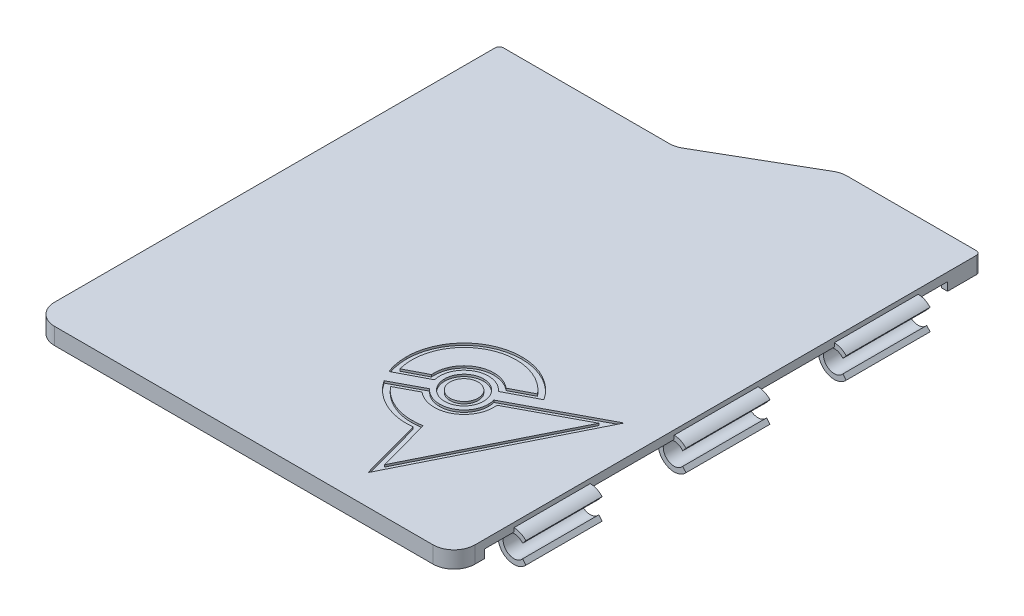
SolidWorks part; units mm, degrees
ref_plane "Front Plane" through (0, 0, 0) normal (0, 0, 1) x (1, 0, 0)
ref_plane "Top Plane" through (0, 0, 0) normal (0, 1, 0) x (1, 0, 0)
ref_plane "Right Plane" through (0, 0, 0) normal (1, 0, 0) x (0, 0, -1)
sketch "Sketch1" plane through (0, 0, 0) normal (0, 1, 0) x (1, 0, 0)
  line L0 (63.6333, 61.8247) -> (63.6333, 80.2409) construction
  line L1 (63.6333, -79.34) -> (-63.6333, -79.34)
  line L2 (63.6333, -79.34) -> (63.6333, 80.0409)
  line L4 (-63.6333, -79.34) -> (-63.6333, 61.6247)
  line L5 (-57.2833, -79.34) -> (57.2833, -79.34) construction
  line L6 (23.1126, 80.2409) -> (62.3633, 80.2409) construction
  line L7 (-63.6333, 92.3071) -> (-63.6333, 63.0947) construction
  line L11 (-63.6333, 61.6247) -> (-10.4331, 61.6247)
  line L12 (21.4647, 80.0409) -> (63.6333, 80.0409)
  line L13 (-10.4331, 61.6247) -> (21.4647, 80.0409)
  line L14 (-9.0132, 62.6755) -> (19.9376, 79.3902) construction
  line L15 (-62.3633, 61.8247) -> (-12.1882, 61.8247) construction
  point P0 (0, 0)
  dimension "D1" = 0.2
  dimension "D2" = 0.2
  dimension "D3" = 0.2
extrude "Boss-Extrude1" add sketch "Sketch1" along normal up to surface (5.0667 mm away)
ref_plane "Plane1" through (0, 0, -61.1897) normal (0, 0, 1) x (1, 0, 0)
sketch "Sketch2" plane through (0, 0, -61.1897) normal (0, 0, 1) x (1, 0, 0)
  circle A0 centre (63.6333, -1.1598) radius 4.826
  circle A1 centre (63.6333, -1.1598) radius 3.302
  point P3 (0, 0)
  point P5 (63.6333, -1.1598)
  dimension "D1" = 9.652
  dimension "D2" = 6.604
extrude "Boss-Extrude2" add sketch "Sketch2" along normal offset from surface (122.3795 mm away) 0.635
sketch "Sketch3" plane through (0, 0, 61.1897) normal (0, 0, 1) x (1, 0, 0)
  arc A0 (60.5417, 0) -> (63.6333, 2.1422) centre (63.6333, -1.1598) ccw construction
  circle A1 centre (63.6333, -1.1598) radius 3.302
extrude "Cut-Extrude1" cut sketch "Sketch3" against normal up to surface (122.3795 mm away) up to face at (63.8751, -1.4825, -61.1897)
sketch "Sketch4" plane through (0, 0, 0) normal (0, -1, 0) x (1, 0, 0)
  line L12 (60.5417, 63.0947) -> (61.7283, 63.0947)
  line L13 (60.5417, 63.0947) -> (61.7283, 63.0947)
  line L14 (61.7283, -63.0947) -> (60.5417, -63.0947)
  line L15 (61.7283, -63.0947) -> (60.5417, -63.0947)
  line L24 (61.7283, 63.0947) -> (61.7283, 77.435)
  line L25 (61.7283, 77.435) -> (-61.7283, 77.435)
  line L26 (-61.7283, 77.435) -> (-61.7283, -59.7197)
  line L27 (-61.7283, -59.7197) -> (-9.9227, -59.7197)
  line L28 (-9.9227, -59.7197) -> (21.9751, -78.1359)
  line L29 (21.9751, -78.1359) -> (61.7283, -78.1359)
  line L30 (61.7283, -78.1359) -> (61.7283, -63.0947)
  line L31 (60.5417, -63.0947) -> (57.0438, -63.0947)
  line L32 (57.0438, -63.0947) -> (57.0438, 63.0947)
  line L33 (57.0438, 63.0947) -> (60.5417, 63.0947)
  line L34 (61.7283, 63.0947) -> (61.7283, 77.435)
  line L35 (61.7283, 77.435) -> (-61.7283, 77.435)
  line L36 (-61.7283, 77.435) -> (-61.7283, -59.7197)
  line L37 (-61.7283, -59.7197) -> (-9.9227, -59.7197)
  line L38 (-9.9227, -59.7197) -> (21.9751, -78.1359)
  line L39 (21.9751, -78.1359) -> (61.7283, -78.1359)
  line L40 (61.7283, -78.1359) -> (61.7283, -63.0947)
  line L41 (60.5417, -63.0947) -> (57.0438, -63.0947)
  line L42 (57.0438, -63.0947) -> (57.0438, 63.0947)
  line L43 (57.0438, 63.0947) -> (60.5417, 63.0947)
  dimension "D1" = 1.905
extrude "Cut-Extrude2" cut sketch "Sketch4" against normal offset from surface (3.1617 mm away) 1.905 up to face at (1.8386, 5.0667, -20.7752)
sketch "Sketch6" plane through (63.6333, 0, 0) normal (1, 0, 0) x (0, 0, -1)
  line L0 (0, 12.3819) -> (0, -18.9186) construction
  line L1 (-61.1897, 0) -> (-70.0797, 0)
  line L2 (-61.1897, 0) -> (-61.1897, 2.54)
  line L3 (-61.1897, 2.54) -> (-70.0797, 2.54)
  line L4 (-70.0797, 0) -> (-70.0797, 2.54)
  line L5 (70.0797, 0) -> (70.0797, 2.54)
  line L6 (61.1897, 2.54) -> (70.0797, 2.54)
  line L7 (61.1897, 0) -> (61.1897, 2.54)
  line L8 (61.1897, 0) -> (70.0797, 0)
  line L9 (-69.4447, 1.905) -> (-69.4447, 0) construction
  line L10 (-69.4447, 1.905) -> (-61.8247, 1.905) construction
  point P14 (-69.4447, 0.9525)
  dimension "D1" = 0.635
  dimension "D2" = 0.635
extrude "Cut-Extrude3" cut sketch "Sketch6" against normal blind 6.35
sketch "Sketch7" plane through (0, 0, 0) normal (0, 0, 1) x (1, 0, 0)
  line L0 (63.6333, 4.337) -> (63.6333, 2.54)
  line L1 (63.6333, 5.0667) -> (63.6333, 0) construction
  line L2 (63.6333, 2.54) -> (61.7283, 2.54)
  line L3 (61.7283, 2.54) -> (61.7283, 3.1617)
  line L4 (61.7283, 3.1617) -> (56.3001, 3.1617)
  line L5 (-61.7283, 3.1617) -> (61.7283, 3.1617) construction
  line L6 (56.3001, 3.1617) -> (56.3001, -6.3518)
  line L7 (56.3001, -6.3518) -> (72.4996, -6.3518)
  line L8 (72.4996, -6.3518) -> (72.4996, 4.337)
  line L9 (72.4996, 4.337) -> (63.6333, 4.337)
ref_plane "Plane2" through (0, 0, 12.7) normal (0, 0, 1) x (1, 0, 0)
ref_plane "Plane3" through (0, 0, -12.7) normal (0, 0, 1) x (1, 0, 0)
sketch "Sketch8" plane through (0, 0, 12.7) normal (0, 0, 1) x (1, 0, 0)
  line L0 (63.6333, 4.337) -> (63.6333, 2.54) construction
  line L1 (72.4996, -6.3518) -> (72.4996, 4.337) construction
  line L2 (72.4996, 4.337) -> (63.6333, 4.337) construction
  line L3 (63.6333, 2.54) -> (61.7283, 2.54) construction
  line L4 (61.7283, 2.54) -> (61.7283, 3.1617) construction
  line L5 (61.7283, 3.1617) -> (56.3001, 3.1617) construction
  line L6 (56.3001, 3.1617) -> (56.3001, -6.3518) construction
  line L7 (56.3001, -6.3518) -> (72.4996, -6.3518) construction
  line L8 (56.3001, -6.3518) -> (72.4996, -6.3518)
  line L9 (56.3001, 3.1617) -> (56.3001, -6.3518)
  line L10 (61.7283, 3.1617) -> (56.3001, 3.1617)
  line L11 (61.7283, 2.54) -> (61.7283, 3.1617)
  line L12 (63.6333, 2.54) -> (61.7283, 2.54)
  line L13 (63.6333, 4.337) -> (63.6333, 2.54)
  line L14 (72.4996, 4.337) -> (63.6333, 4.337)
  line L15 (72.4996, -6.3518) -> (72.4996, 4.337)
sketch "Sketch9" plane through (0, 0, -12.7) normal (0, 0, 1) x (1, 0, 0)
  line L0 (72.4996, -6.3518) -> (72.4996, 4.337) construction
  line L1 (72.4996, 4.337) -> (63.6333, 4.337) construction
  line L2 (63.6333, 4.337) -> (63.6333, 2.54) construction
  line L3 (63.6333, 2.54) -> (61.7283, 2.54) construction
  line L4 (61.7283, 2.54) -> (61.7283, 3.1617) construction
  line L5 (61.7283, 3.1617) -> (56.3001, 3.1617) construction
  line L6 (56.3001, 3.1617) -> (56.3001, -6.3518) construction
  line L7 (56.3001, -6.3518) -> (72.4996, -6.3518) construction
  line L8 (72.4996, -6.3518) -> (72.4996, 4.337)
  line L9 (56.3001, -6.3518) -> (72.4996, -6.3518)
  line L10 (56.3001, 3.1617) -> (56.3001, -6.3518)
  line L11 (61.7283, 3.1617) -> (56.3001, 3.1617)
  line L12 (61.7283, 2.54) -> (61.7283, 3.1617)
  line L13 (63.6333, 2.54) -> (61.7283, 2.54)
  line L14 (63.6333, 4.337) -> (63.6333, 2.54)
  line L15 (72.4996, 4.337) -> (63.6333, 4.337)
extrude "Cut-Extrude4" cut sketch "Sketch9" against normal offset from surface (23.0897 mm away) 25.4
extrude "Cut-Extrude5" cut sketch "Sketch8" along normal blind 25.4
sketch "Sketch10" plane through (0, 0, 0) normal (0, -1, 0) x (1, 0, 0)
  line L0 (61.7283, 63.0947) -> (61.7283, 61.1897)
  line L1 (57.2833, 61.1897) -> (63.6333, 61.1897) construction
  line L2 (61.7283, 61.1897) -> (58.9488, 61.1897)
  line L3 (58.9488, 61.1897) -> (58.9488, -61.1897)
  line L4 (58.9488, -61.1897) -> (58.9488, -35.7897) construction
  line L5 (58.9488, -61.1897) -> (61.7283, -61.1897)
  line L6 (61.7283, -61.1897) -> (61.7283, -63.0947)
  line L7 (61.7283, -63.0947) -> (57.0438, -63.0947)
  line L8 (57.0438, -63.0947) -> (57.0438, 63.0947)
  line L9 (57.0438, 63.0947) -> (61.7283, 63.0947)
  line L10 (57.0438, 61.1897) -> (57.0438, 63.0947) construction
  line L11 (57.0438, 63.0947) -> (57.0438, 38.1) construction
  line L12 (58.8073, -61.1897) -> (68.4593, -61.1897) construction
extrude "Cut-Extrude6" cut sketch "Sketch10" against normal up to surface (3.1617 mm away) up to face at (40.2603, 3.1617, -6.4567)
sketch "Sketch11" plane through (0, 0, -33.9396) normal (-1, 0, 0) x (0, 0, 1)
  line L0 (-46.1013, 0) -> (-27.6851, 0) construction
  line L1 (-27.8851, 0) -> (-36.1401, 0)
  line L2 (-27.8851, 0) -> (-27.8851, 3.1617)
  line L3 (-27.8851, 3.1617) -> (-36.1401, 3.1617)
  line L4 (-36.1401, 0) -> (-36.1401, 3.1617)
  line L5 (-44.1963, 3.1617) -> (-25.7801, 3.1617) construction
  line L6 (-35.5051, 1.905) -> (-35.5051, 0) construction
  line L7 (-27.8851, 5.0667) -> (-27.8851, 1.905) construction
  dimension "D1" = 0.635
sketch "Sketch12" plane through (0, 0, -61.6247) normal (0, 0, -1) x (-1, 0, 0)
  line L0 (10.4331, 0) -> (63.6333, 0) construction
  line L1 (37.665, 0) -> (46.555, 0)
  line L2 (37.665, 0) -> (37.665, 3.1617)
  line L3 (37.665, 3.1617) -> (46.555, 3.1617)
  line L4 (46.555, 0) -> (46.555, 3.1617)
  line L5 (9.9227, 3.1617) -> (61.7283, 3.1617) construction
  line L6 (45.92, 0) -> (45.92, 1.905) construction
  line L7 (38.3, -1.905) -> (38.3, 1.905) construction
  dimension "D1" = 0.635
  dimension "D2" = 0.635
extrude "Cut-Extrude7" cut sketch "Sketch11" against normal mid plane 25.4
extrude "Cut-Extrude8" cut sketch "Sketch12" against normal mid plane 6.35
sketch "Sketch13" plane through (0, 0, 0) normal (0, 0, 1) x (1, 0, 0)
  line L0 (66.2361, -3.1918) -> (66.2361, 0.8722)
  line L2 (66.2361, 0.8722) -> (69.8032, 5.1234)
  line L3 (69.8032, 5.1234) -> (69.8032, -7.4429)
  line L4 (69.8032, -7.4429) -> (66.2361, -3.1918)
  line L6 (63.6333, 5.0667) -> (63.6333, 0) construction
  circle A1 centre (63.6333, -1.1598) radius 3.302 construction
  point P4 (65.744, 1.3796)
  point P6 (69.6367, 5.6662)
  point P8 (69.2446, -7.5737)
  dimension "D1" = 4.064
  dimension "D2" = 40
  dimension "D3" = 40
extrude "Cut-Extrude9" cut sketch "Sketch13" along normal up to surface (61.1897 mm away) and the other way up to surface (61.1897 mm away) up to face at (62.3229, 1.3794, 61.1897) other way up to face at (62.3229, 1.3794, -61.1897)
sketch "Sketch14" plane through (0, 0, 0) normal (0, 0, 1) x (1, 0, 0)
  line L1 (63.6333, 2.54) -> (65.2236, 2.54)
  line L2 (63.6333, 2.54) -> (63.6333, 3.2073)
  line L3 (63.6333, 3.2073) -> (65.2236, 3.2073)
  line L4 (65.2236, 2.54) -> (65.2236, 3.2073)
extrude "Cut-Extrude10" [suppressed] cut sketch "Sketch14" against normal up to surface and the other way up to surface
fillet "Fillet1" radius 6.35 2 edges at (-63.6333, 2.5333, 79.34) (63.6333, 2.5333, 79.34)
fillet "Fillet2" radius 6.35 2 edges at (21.4647, 2.5333, -80.0409) (-10.4331, 2.5333, -61.6247)
fillet "Fillet3" radius 1.27 2 edges at (-63.6333, 2.5333, -61.6247) (63.6333, 2.5333, -80.0409)
sketch "Sketch16" plane through (0, 5.0667, 0) normal (0, 1, 0) x (1, 0, 0)
  line L0 (54.61, -71.0546) -> (0, -71.0546) construction
  line L1 (54.61, -71.0546) -> (54.61, -16.4446) construction
  line L2 (54.61, -16.4446) -> (0, -16.4446) construction
  line L3 (0, -71.0546) -> (0, -16.4446) construction
  dimension "D1" = 54.61
sketch "Sketch15" plane through (0, 5.0667, 0) normal (0, 1, 0) x (1, 0, 0)
  line L0 (33.5489, -23.9385) -> (27.2661, -27.2053)
  line L1 (12.4152, -34.927) -> (6.1279, -38.1961)
  line L2 (5.1765, -40.5517) -> (14.2397, -35.8392)
  line L3 (26.9642, -29.223) -> (36.0259, -24.5113)
  line L4 (50.4821, -22.3569) -> (28.936, -65.6472)
  line L5 (28.936, -65.6472) -> (24.558, -49.6369)
  line L6 (24.558, -49.6369) -> (23.1566, -49.7913)
  line L7 (9.312, -44.2699) -> (15.5544, -40.9474)
  line L8 (30.3749, -33.0591) -> (50.4821, -22.3569)
  line L9 (54.2571, -18.4773) -> (28.5326, -32.1694)
  line L10 (15.8459, -38.922) -> (6.8377, -43.7167)
  line L11 (23.3374, -51.4324) -> (28.4853, -70.2581)
  line L12 (28.4853, -70.2581) -> (54.2571, -18.4773)
  spline S0 degree 3 poles (21.403, -18.2519) (24.0761, -18.2519) (26.7171, -18.9307) (29.0406, -20.2149) knots 0 0 0 0 1 1 1 1
  spline S1 degree 3 poles (29.0406, -20.2149) (30.7573, -21.1637) (32.291, -22.4336) (33.5489, -23.9385) knots 1 1 1 1 2 2 2 2
  spline S2 degree 3 poles (27.2661, -27.2053) (25.6418, -25.8181) (23.5665, -25.0419) (21.403, -25.0419) knots 3 3 3 3 4 4 4 4
  spline S3 degree 3 poles (21.403, -25.0419) (20.1849, -25.0419) (19.0024, -25.2809) (17.8883, -25.7521) knots 4 4 4 4 5 5 5 5
  spline S4 degree 3 poles (17.8883, -25.7521) (16.813, -26.2069) (15.8476, -26.8577) (15.019, -27.6863) knots 5 5 5 5 6 6 6 6
  spline S5 degree 3 poles (15.019, -27.6863) (14.1904, -28.5149) (13.5397, -29.4802) (13.0848, -30.5555) knots 6 6 6 6 7 7 7 7
  spline S6 degree 3 poles (13.0848, -30.5555) (12.6136, -31.6696) (12.3747, -32.8522) (12.3747, -34.0702) knots 7 7 7 7 8 8 8 8
  spline S7 degree 3 poles (12.3747, -34.0702) (12.3747, -34.3565) (12.3883, -34.6425) (12.4152, -34.927) knots 8 8 8 8 9 9 9 9
  spline S8 degree 3 poles (6.1279, -38.1961) (5.7669, -36.8585) (5.5847, -35.4771) (5.5847, -34.0702) knots 10 10 10 10 11 11 11 11
  spline S9 degree 3 poles (5.5847, -34.0702) (5.5847, -31.934) (6.0027, -29.8627) (6.8271, -27.9135) knots 11 11 11 11 12 12 12 12
  spline S10 degree 3 poles (6.8271, -27.9135) (7.6237, -26.0301) (8.7645, -24.3383) (10.2178, -22.885) knots 12 12 12 12 13 13 13 13
  spline S11 degree 3 poles (10.2178, -22.885) (11.671, -21.4318) (13.3629, -20.291) (15.2463, -19.4944) knots 13 13 13 13 14 14 14 14
  spline S12 degree 3 poles (15.2463, -19.4944) (17.1954, -18.67) (19.2668, -18.2519) (21.403, -18.2519) knots 14 14 14 14 15 15 15 15
  spline S13 degree 3 poles (21.403, -16.601) (11.755, -16.601) (3.9337, -24.4222) (3.9337, -34.0702) knots 0 0 0 0 1 1 1 1
  spline S14 degree 3 poles (3.9337, -34.0702) (3.9337, -36.3605) (4.3752, -38.5475) (5.1765, -40.5517) knots 1 1 1 1 2 2 2 2
  spline S15 degree 3 poles (14.2397, -35.8392) (14.1002, -35.2724) (14.0257, -34.6801) (14.0257, -34.0702) knots 3 3 3 3 4 4 4 4
  spline S16 degree 3 poles (14.0257, -34.0702) (14.0257, -29.9959) (17.3286, -26.6929) (21.403, -26.6929) knots 4 4 4 4 5 5 5 5
  spline S17 degree 3 poles (21.403, -26.6929) (23.6219, -26.6929) (25.6118, -27.6727) (26.9642, -29.223) knots 5 5 5 5 6 6 6 6
  spline S18 degree 3 poles (36.0259, -24.5113) (32.9059, -19.7481) (27.5224, -16.601) (21.403, -16.601) knots 7 7 7 7 8 8 8 8
  spline S19 degree 3 poles (23.1566, -49.7913) (22.5712, -49.8558) (21.9812, -49.8885) (21.403, -49.8885) knots 3 3 3 3 4 4 4 4
  spline S20 degree 3 poles (21.403, -49.8885) (16.7028, -49.8885) (12.303, -47.8173) (9.312, -44.2699) knots 4 4 4 4 5 5 5 5
  spline S21 degree 3 poles (15.5544, -40.9474) (17.1766, -42.327) (19.2462, -43.0985) (21.403, -43.0985) knots 6 6 6 6 7 7 7 7
  spline S22 degree 3 poles (21.403, -43.0985) (22.6211, -43.0985) (23.8036, -42.8596) (24.9177, -42.3884) knots 7 7 7 7 8 8 8 8
  spline S23 degree 3 poles (24.9177, -42.3884) (25.993, -41.9336) (26.9583, -41.2828) (27.787, -40.4542) knots 8 8 8 8 9 9 9 9
  spline S24 degree 3 poles (27.787, -40.4542) (28.6156, -39.6256) (29.2663, -38.6602) (29.7211, -37.585) knots 9 9 9 9 10 10 10 10
  spline S25 degree 3 poles (29.7211, -37.585) (30.1924, -36.4708) (30.4313, -35.2883) (30.4313, -34.0702) knots 10 10 10 10 11 11 11 11
  spline S26 degree 3 poles (30.4313, -34.0702) (30.4313, -33.7319) (30.4124, -33.3943) (30.3749, -33.0591) knots 11 11 11 11 12 12 12 12
  spline S27 degree 3 poles (28.5326, -32.1694) (28.6939, -32.7759) (28.7803, -33.4129) (28.7803, -34.0702) knots 1 1 1 1 2 2 2 2
  spline S28 degree 3 poles (28.7803, -34.0702) (28.7803, -38.1446) (25.4774, -41.4475) (21.403, -41.4475) knots 2 2 2 2 3 3 3 3
  spline S29 degree 3 poles (21.403, -41.4475) (19.1863, -41.4475) (17.1982, -40.4697) (15.8459, -38.922) knots 3 3 3 3 4 4 4 4
  spline S30 degree 3 poles (6.8377, -43.7167) (6.838, -43.7172) (6.8384, -43.7178) (6.8388, -43.7183) knots 5 5 5 5 6 6 6 6
  spline S31 degree 3 poles (6.8388, -43.7183) (9.9674, -48.4316) (15.3219, -51.5395) (21.403, -51.5395) knots 6 6 6 6 7 7 7 7
  spline S32 degree 3 poles (21.403, -51.5395) (22.0569, -51.5395) (22.7021, -51.5024) (23.3374, -51.4324) knots 7 7 7 7 8 8 8 8
  spline S33 degree 3 poles (21.403, -38.3156) (19.0621, -38.3156) (17.1576, -36.4111) (17.1576, -34.0702) (17.1576, -31.7293) (19.0621, -29.8249) (21.403, -29.8249) knots 2 2 2 2 3 3 3 4 4 4 4
  spline S34 degree 3 poles (21.403, -29.8249) (23.7439, -29.8249) (25.6484, -31.7293) (25.6484, -34.0702) (25.6484, -36.4111) (23.7439, -38.3156) (21.403, -38.3156) knots 0 0 0 0 1 1 1 2 2 2 2
  spline S35 degree 3 poles (21.403, -28.1739) (18.1465, -28.1739) (15.5066, -30.8138) (15.5066, -34.0702) knots 0 0 0 0 1 1 1 1
  spline S36 degree 3 poles (15.5066, -34.0702) (15.5066, -37.3267) (18.1465, -39.9666) (21.403, -39.9666) knots 1 1 1 1 2 2 2 2
  spline S37 degree 3 poles (21.403, -39.9666) (24.6595, -39.9666) (27.2994, -37.3267) (27.2994, -34.0702) knots 2 2 2 2 3 3 3 3
  spline S38 degree 3 poles (27.2994, -34.0702) (27.2994, -30.8138) (24.6595, -28.1739) (21.403, -28.1739) knots 3 3 3 3 4 4 4 4
  point P52 (33.8942, -42.3884)
extrude "Cut-Extrude11" cut sketch "Sketch15" against normal blind 0.635
sketch "Sketch17" plane through (0, 5.0667, 0) normal (0, 1, 0) x (1, 0, 0)
  line L0 (36.4563, -27.8134) -> (51.2602, -22.7812)
  line L1 (51.2602, -22.7812) -> (38.3088, -32.0938)
  line L2 (38.3912, -32.3506) -> (44.4207, -32.3671)
  line L3 (44.4207, -32.3671) -> (34.9383, -35.9917)
  line L4 (34.9247, -36.2505) -> (36.7174, -37.1613)
  line L5 (36.7194, -37.2866) -> (27.2269, -42.4955)
  line L6 (26.8154, -42.4942) -> (17.4652, -37.2866)
  line L7 (17.4673, -37.1613) -> (19.2599, -36.2505)
  line L8 (19.2463, -35.9917) -> (9.0534, -32.3671)
  line L9 (9.0534, -32.3671) -> (15.2248, -32.3506)
  line L10 (15.3072, -32.0938) -> (2.3558, -22.7812)
  line L11 (2.3558, -22.7812) -> (17.1597, -27.8134)
  line L12 (17.346, -27.6788) -> (17.346, -26.9097)
  line L13 (17.346, -26.9097) -> (22.8389, -30.5421)
  line L14 (22.8389, -30.5421) -> (18.9939, -34.5466)
  line L15 (18.9939, -34.5466) -> (23.9552, -33.4657)
  line L16 (23.9552, -33.4657) -> (24.4868, -35.592)
  line L17 (24.4868, -35.592) -> (26.046, -33.1113)
  line L18 (26.046, -33.1113) -> (24.7348, -34.2099)
  line L19 (24.7348, -34.2099) -> (24.5095, -32.8415)
  line L20 (24.3487, -32.7243) -> (21.0316, -33.2176)
  line L21 (21.0316, -33.2176) -> (23.687, -30.5789)
  line L22 (23.6597, -30.2543) -> (18.9939, -26.9629)
  line L23 (18.9939, -26.9629) -> (23.052, -27.9964)
  line L24 (23.2114, -27.8076) -> (22.5023, -26.1478)
  line L25 (22.5023, -26.1478) -> (24.4496, -27.4008)
  line L26 (24.6607, -27.2368) -> (21.9707, -19.1666)
  line L27 (21.9707, -19.1666) -> (26.8436, -26.2541)
  line L28 (26.8436, -26.2541) -> (31.7872, -19.1666)
  line L29 (31.7872, -19.1666) -> (29.0971, -27.2368)
  line L30 (29.3083, -27.4008) -> (31.2556, -26.1478)
  line L31 (31.2556, -26.1478) -> (30.6883, -27.6657)
  line L32 (30.8478, -27.8545) -> (34.7639, -27.1047)
  line L33 (34.7639, -27.1047) -> (30.0982, -30.2543)
  line L34 (30.0709, -30.5789) -> (32.7263, -33.2176)
  line L35 (32.7263, -33.2176) -> (29.4092, -32.7243)
  line L36 (29.2484, -32.8415) -> (29.023, -34.2099)
  line L37 (29.023, -34.2099) -> (27.7118, -33.1113)
  line L38 (27.7118, -33.1113) -> (29.2711, -35.592)
  line L39 (29.2711, -35.592) -> (29.8027, -33.4657)
  line L40 (29.8027, -33.4657) -> (34.7639, -34.5466)
  line L41 (34.7639, -34.5466) -> (30.9189, -30.5421)
  line L42 (30.9189, -30.5421) -> (36.27, -26.9097)
  line L43 (36.27, -26.9097) -> (36.27, -27.6788)
  line L44 (26.1526, -31.2627) -> (26.9979, -40.5001)
  line L45 (26.9979, -40.5001) -> (27.6291, -31.2627)
  line L46 (31.8621, -45.8746) -> (36.9965, -47.1624)
  line L47 (36.9965, -47.1624) -> (29.3242, -42.6086)
  line L48 (29.3242, -42.6086) -> (27.2953, -43.6855)
  line L49 (26.7503, -43.6782) -> (24.8591, -42.6086)
  line L50 (24.8591, -42.6086) -> (17.1868, -47.2332)
  line L51 (17.1868, -47.2332) -> (22.3301, -45.9923)
  line L52 (22.5712, -46.292) -> (20.6066, -50.334)
  line L53 (20.6066, -50.334) -> (24.8552, -47.5909)
  line L54 (25.1773, -47.7198) -> (27.1625, -55.9864)
  line L55 (27.1625, -55.9864) -> (29.1987, -47.7394)
  line L56 (29.5229, -47.6134) -> (33.7185, -50.405)
  line L57 (33.7185, -50.405) -> (31.6199, -46.1753)
  line L58 (55.3001, -18.2807) -> (53.5636, -21.6118)
  line L59 (53.5636, -21.6118) -> (52.2879, -21.9662)
  line L60 (52.2879, -21.9662) -> (53.2801, -19.9462)
  line L61 (53.2801, -19.9462) -> (34.2855, -25.2619)
  line L62 (34.2855, -25.2619) -> (34.888, -24.0217)
  line L63 (34.888, -24.0217) -> (55.3001, -18.2807)
  line L64 (44.5624, -35.1136) -> (27.0208, -66.0152)
  line L65 (27.0208, -66.0152) -> (9.3373, -35.1136)
  line L66 (9.3373, -35.1136) -> (8.3805, -34.9364)
  line L67 (8.3805, -34.9364) -> (12.2786, -41.8467)
  line L68 (12.2786, -41.8467) -> (10.0458, -40.8544)
  line L69 (10.0458, -40.8544) -> (27.0208, -70.5867)
  line L70 (27.0208, -70.5867) -> (43.8539, -40.8544)
  line L71 (43.8539, -40.8544) -> (41.6211, -41.8467)
  line L72 (41.6211, -41.8467) -> (45.5193, -34.9364)
  line L73 (45.5193, -34.9364) -> (44.5624, -35.1136)
  line L74 (18.7874, -25.0256) -> (18.185, -23.7854)
  line L75 (18.185, -23.7854) -> (-1.4057, -18.2807)
  line L76 (-1.4057, -18.2807) -> (0.5016, -21.8599)
  line L77 (0.5016, -21.8599) -> (1.7774, -22.2142)
  line L78 (1.7774, -22.2142) -> (0.6143, -19.9462)
  line L79 (0.6143, -19.9462) -> (18.7874, -25.0256)
  spline S0 degree 3 poles (38.3088, -32.0938) (38.1972, -32.174) (38.2537, -32.3503) (38.3912, -32.3506) knots 2 2 2 2 3 3 3 3
  spline S1 degree 3 poles (34.9383, -35.9917) (34.8235, -36.0356) (34.8151, -36.1949) (34.9247, -36.2505) knots 5 5 5 5 6 6 6 6
  spline S2 degree 3 poles (36.7174, -37.1613) (36.7682, -37.1871) (36.7693, -37.2593) (36.7194, -37.2866) knots 7 7 7 7 8 8 8 8
  spline S3 degree 3 poles (27.2269, -42.4955) (27.0986, -42.5659) (26.9432, -42.5654) (26.8154, -42.4942) knots 9 9 9 9 10 10 10 10
  spline S4 degree 3 poles (17.4652, -37.2866) (17.4153, -37.2593) (17.4165, -37.1871) (17.4673, -37.1613) knots 11 11 11 11 12 12 12 12
  spline S5 degree 3 poles (19.2599, -36.2505) (19.3695, -36.1949) (19.3612, -36.0356) (19.2463, -35.9917) knots 13 13 13 13 14 14 14 14
  spline S6 degree 3 poles (15.2248, -32.3506) (15.3623, -32.3503) (15.4188, -32.174) (15.3072, -32.0938) knots 16 16 16 16 17 17 17 17
  spline S7 degree 3 poles (17.1597, -27.8134) (17.2514, -27.8437) (17.346, -27.7755) (17.346, -27.6788) knots 19 19 19 19 20 20 20 20
  spline S8 degree 3 poles (24.5095, -32.8415) (24.4969, -32.7651) (24.4253, -32.7129) (24.3487, -32.7243) knots 28 28 28 28 29 29 29 29
  spline S9 degree 3 poles (23.687, -30.5789) (23.7807, -30.4857) (23.7676, -30.3305) (23.6597, -30.2543) knots 31 31 31 31 32 32 32 32
  spline S10 degree 3 poles (23.052, -27.9964) (23.1606, -28.0172) (23.2501, -27.9112) (23.2114, -27.8076) knots 34 34 34 34 35 35 35 35
  spline S11 degree 3 poles (24.4496, -27.4008) (24.5621, -27.4732) (24.703, -27.3637) (24.6607, -27.2368) knots 37 37 37 37 38 38 38 38
  spline S12 degree 3 poles (29.0971, -27.2368) (29.0548, -27.3637) (29.1958, -27.4732) (29.3083, -27.4008) knots 42 42 42 42 43 43 43 43
  spline S13 degree 3 poles (30.6883, -27.6657) (30.6496, -27.7693) (30.7391, -27.8753) (30.8478, -27.8545) knots 45 45 45 45 46 46 46 46
  spline S14 degree 3 poles (30.0982, -30.2543) (29.9902, -30.3305) (29.9772, -30.4857) (30.0709, -30.5789) knots 48 48 48 48 49 49 49 49
  spline S15 degree 3 poles (29.4092, -32.7243) (29.3326, -32.7129) (29.261, -32.7651) (29.2484, -32.8415) knots 51 51 51 51 52 52 52 52
  spline S16 degree 3 poles (36.27, -27.6788) (36.27, -27.7755) (36.3646, -27.8437) (36.4563, -27.8134) knots 60 60 60 60 61 61 61 61
  spline S17 degree 2 poles (27.6291, -31.2627) (27.198, -30.9792) (26.8909, -30.4358) knots 0 0 0 1 1 1
  spline S18 degree 2 poles (26.8909, -30.4358) (26.5837, -30.9792) (26.1526, -31.2627) knots 1 1 1 2 2 2
  spline S19 degree 3 poles (27.2953, -43.6855) (27.1243, -43.7763) (26.9188, -43.7735) (26.7503, -43.6782) knots 3 3 3 3 4 4 4 4
  spline S20 degree 3 poles (22.3301, -45.9923) (22.5048, -45.9502) (22.6498, -46.1303) (22.5712, -46.292) knots 7 7 7 7 8 8 8 8
  spline S21 degree 3 poles (24.8552, -47.5909) (24.9784, -47.5114) (25.1431, -47.5774) (25.1773, -47.7198) knots 10 10 10 10 11 11 11 11
  spline S22 degree 3 poles (29.1987, -47.7394) (29.234, -47.5965) (29.4004, -47.5318) (29.5229, -47.6134) knots 13 13 13 13 14 14 14 14
  spline S23 degree 3 poles (31.6199, -46.1753) (31.5393, -46.0128) (31.6861, -45.8304) (31.8621, -45.8746) knots 16 16 16 16 17 17 17 17
extrude "Cut-Extrude12" [suppressed] cut sketch "Sketch17" against normal blind 0.635
sketch "Sketch18" plane through (0, 0, 0) normal (0, 1, 0) x (1, 0, 0)
  line L1 (77.675, 18.4651) -> (57.2549, 18.4651)
  line L2 (77.675, 18.4651) -> (77.675, -16.4467)
  line L3 (77.675, -16.4467) -> (57.2549, -16.4467)
  line L4 (57.2549, 18.4651) -> (57.2549, -16.4467)
  line L5 (-101.4953, 92.2411) -> (103.3649, 92.2411)
  line L6 (-101.4953, 92.2411) -> (-101.4953, -89.3445)
  line L7 (-101.4953, -89.3445) -> (103.3649, -89.3445)
  line L8 (103.3649, 92.2411) -> (103.3649, -89.3445)
extrude "Cut-Extrude13" [suppressed] cut sketch "Sketch18" against normal through all both and the other way through all
